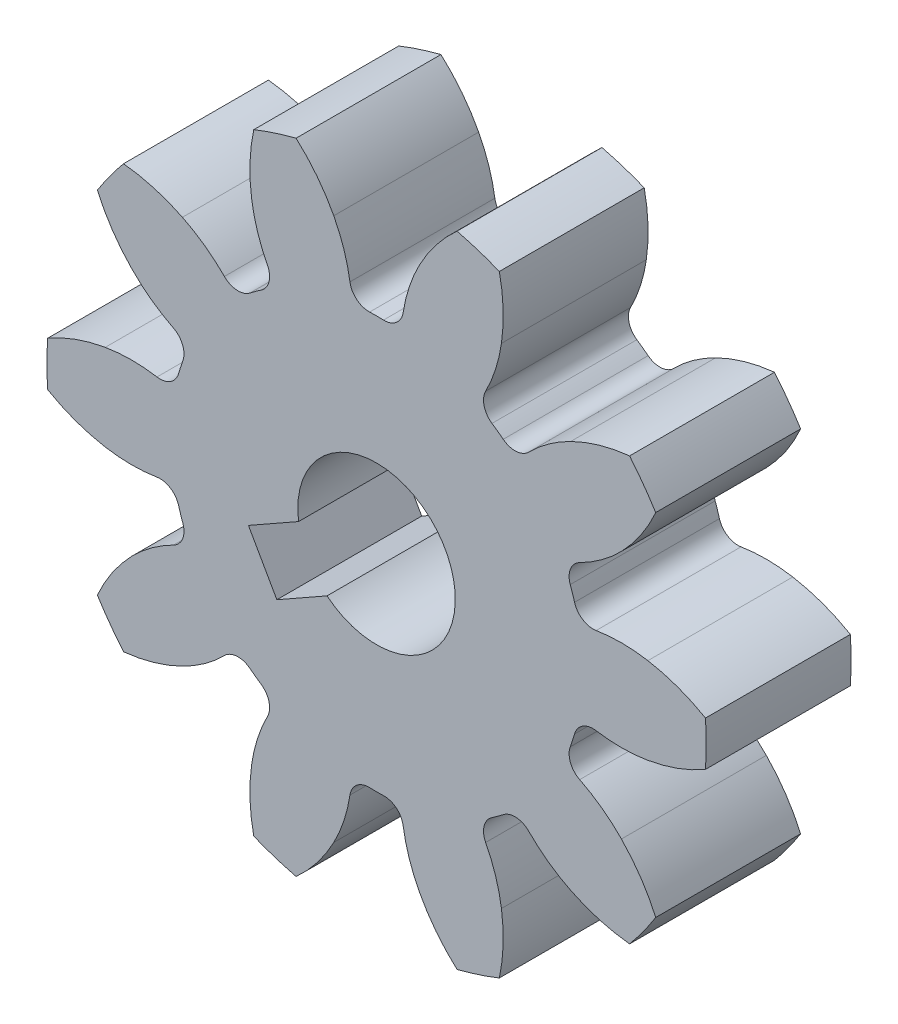
SolidWorks part; units mm, degrees
ref_plane "Front" through (0, 0, 0) normal (0, 0, 1) x (1, 0, 0)
ref_plane "Top" through (0, 0, 0) normal (0, 1, 0) x (1, 0, 0)
ref_plane "Right" through (0, 0, 0) normal (1, 0, 0) x (0, 0, -1)
sketch "Sketch1" plane through (0, 0, 0) normal (0, 0, 1) x (1, 0, 0)
  line L0 (0, 0) -> (11.0772, 0) construction
  line L1 (11.0772, 0) -> (13.2927, 0) construction
  circle A0 centre (0, 0) radius 11.0772 construction
  circle A1 centre (0, 0) radius 13.2927
  dimension "pitch_diameter" = 22.1544
  dimension "addendum" = 2.2154
extrude "GEAR_BASE" add sketch "Sketch1" along normal mid plane 5.842
sketch "Sketch2" plane through (0, 0, 2.921) normal (0, 0, 1) x (1, 0, 0)
  line L0 (0, 0) -> (8.3079, 0) construction
  line L1 (8.3079, 0) -> (11.0772, 0) construction
  line L2 (0, 0) -> (-13.2927, 0) construction
  line L3 (0, 0) -> (-10.754, -7.8132) construction
  line L4 (-11.2565, -7.0701) -> (-9.8733, -5.0223) construction
  line L5 (-9.8733, -5.0223) -> (-7.5942, -3.3688) construction
  line L6 (-13.2624, -0.8966) -> (-10.9397, -1.7402) construction
  line L7 (-10.9397, -1.7402) -> (-8.124, -1.7383) construction
  line L8 (-8.8504, -6.4302) -> (-9.8733, -5.0223) construction
  line L9 (-10.9397, -1.7402) -> (-10.9397, 0) construction
  line L12 (0, 0) -> (-10.9397, -1.7402) construction
  line L13 (0, 0) -> (-9.8733, -5.0223) construction
  line L14 (-9.8733, -5.0223) -> (-6.5418, -11.5715) construction
  line L15 (-10.9397, -1.7402) -> (-12.094, 5.5163) construction
  line L16 (-9.8733, -5.0223) -> (-10.9397, -1.7402) construction
  line L17 (-7.9013, -2.5673) -> (-8.124, -1.7383) construction
  line L18 (-7.9013, -2.5673) -> (-7.5942, -3.3688) construction
  circle A0 centre (0, 0) radius 11.0772 construction
  circle A1 centre (0, 0) radius 8.3079 construction
  circle A2 centre (0, 0) radius 13.2927 construction
  arc A3 (-11.2565, -7.0701) -> (-13.2624, -0.8966) centre (0, 0) cw
  arc A4 (-7.5942, -3.3688) -> (-8.124, -1.7383) centre (0, 0) cw construction
  arc A6 (-11.2565, -7.0701) -> (-9.8733, -5.0223) centre (-4.8882, -9.8807) cw
  arc A7 (-13.2624, -0.8966) -> (-10.9397, -1.7402) centre (-9.7624, 5.1204) ccw
  arc A8 (-9.8733, -5.0223) -> (-8.1904, -3.789) centre (-5.3469, -9.4337) cw
  arc A9 (-10.9397, -1.7402) -> (-8.8533, -1.7489) centre (-9.8707, 4.4892) ccw
  arc A10 (-8.1904, -3.789) -> (-7.8103, -2.8321) centre (-8.5392, -3.0965) ccw
  arc A11 (-8.8533, -1.7489) -> (-7.9833, -2.2995) centre (-8.7284, -2.5141) cw
  arc A12 (-7.8103, -2.8321) -> (-7.9833, -2.2995) centre (0, 0) cw
  dimension "base_fillet" = 0.7754
  dimension "D12" = 6.9609
  dimension "deddendum" = 2.7693
  dimension "D3" = 36
  dimension "D4" = 1.7402
  dimension "D5" = 1.7402
  dimension "D11" = 3.451
  dimension "Pressure_Angle" = 20
  dimension "D14" = 9
  dimension "D15" = 9
extrude "GEAR_CUT" cut sketch "Sketch2" against normal through all
ref_axis "GEAR_AXIS" through (0, 0, 50) along (0, 0, -1)
pattern_circular "GEAR_TEETH" count 10 over 360 about axis through (0, 0, 50) along (0, 0, -1) of "GEAR_CUT"
sketch "Sketch9" plane through (0, 0, -2.921) normal (0, 0, -1) x (-1, 0, 0)
  line L1 (0, 0) -> (1.9981, -2.4674) construction
  line L2 (0, 0) -> (3.1436, -0.4451) construction
  line L4 (1.9981, -2.4674) -> (3.1436, -0.4451) construction
  line L5 (1.9981, -2.4674) -> (3.1436, -0.4451)
  line L6 (1.9981, -2.4674) -> (4.0204, -3.613)
  line L7 (3.1436, -0.4451) -> (5.166, -1.5906)
  line L8 (4.0204, -3.613) -> (5.166, -1.5906)
  circle A0 centre (0, 0) radius 3.175
  dimension "D1" = 6.35
  dimension "D2" = 2.3243
extrude "Cut-Extrude2" cut sketch "Sketch9" against normal through all contours A0 | A0 | A0 | A0 | A0 L8 L7 | A0 L6 L8 region at (0.0291, 0.0165, -2.921) region at (-3.6456, -2.065, -2.921) region at (-2.6478, -1.4998, -2.921)
equation "\"N_teeth\"= 10"
equation "\"pitch_diameter\"=0.872222"
equation "\"Pd\"=\"N_teeth\"/\"pitch_diameter\""
equation "\"addendum\"=1.000/\"Pd\""
equation "\"face_width\"=0.23"
equation "\"deddendum\"=1.250/\"Pd\""
equation "\"D3@Sketch2\" = 360/\"N_teeth\""
equation "\"tooth_thickness\"=1.571/\"Pd\""
equation "\"D4@Sketch2\" = \"tooth_thickness\"/2"
equation "\"D5@Sketch2\" = \"tooth_thickness\"/2"
equation "\"Pressure_Angle\"=20.000000"
equation "\"base_fillet\"=0.35/\"Pd\""
equation "\"D12@Sketch2\" = 2*\"tooth_thickness\""
equation "\"hub_diameter\"=1.57"
equation "\"bore\"=6.35"
equation "\"hub_projection\"=0.250000"
equation "\"sss_diam\"=0.062500"
